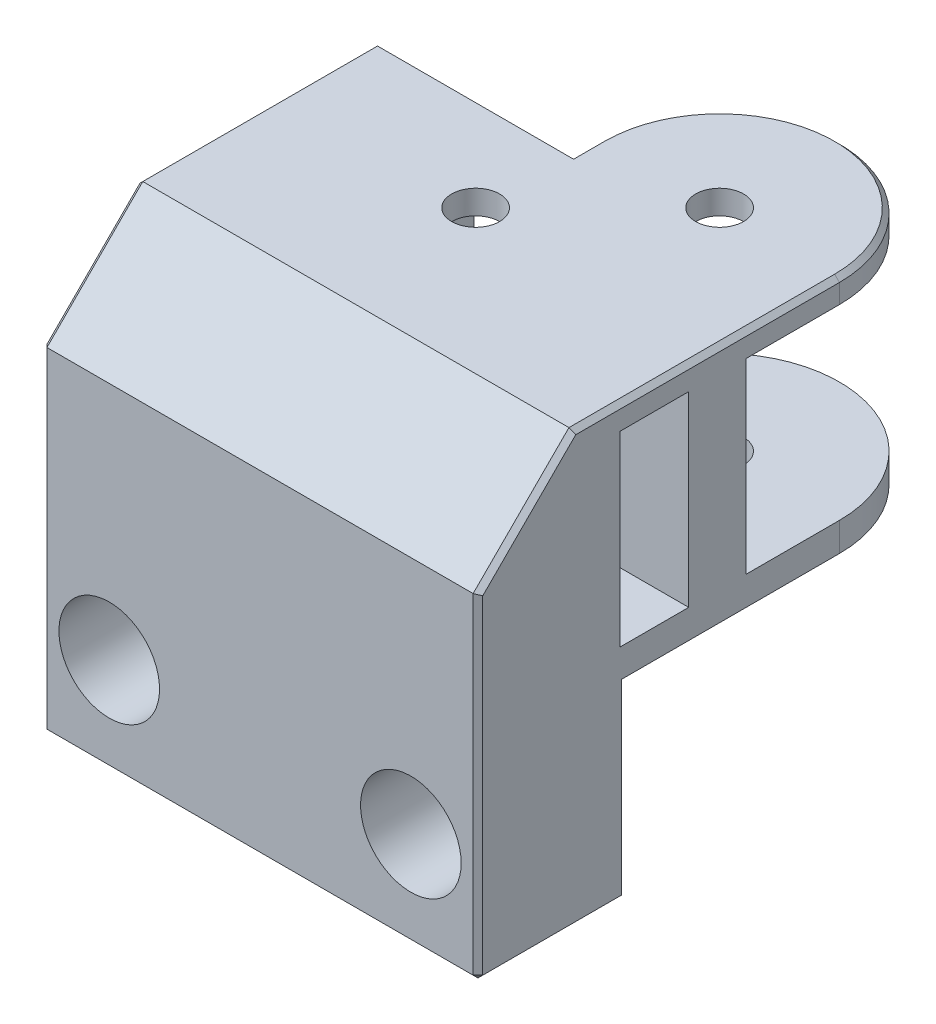
SolidWorks part; units mm, degrees
ref_plane "Front Plane" through (0, 0, 0) normal (0, 0, 1) x (1, 0, 0)
ref_plane "Top Plane" through (0, 0, 0) normal (0, 1, 0) x (1, 0, 0)
ref_plane "Right Plane" through (0, 0, 0) normal (1, 0, 0) x (0, 0, -1)
sketch "Sketch1" plane through (0, 0, 0) normal (0, 1, 0) x (1, 0, 0)
  line L0 (0, 0) -> (-20.24, 0) construction
  line L1 (20.24, -10) -> (25.24, -10)
  line L2 (-20.24, 10) -> (20.24, 10)
  line L3 (-20.24, 10) -> (-20.24, -10)
  line L4 (-20.24, -10) -> (20.24, -10)
  line L5 (20.24, 10) -> (20.24, -10) construction
  line L6 (-20.24, 10) -> (20.24, -10) construction
  line L7 (-20.24, -10) -> (20.24, 10) construction
  line L8 (25.24, -10) -> (25.24, 10)
  line L9 (25.24, 10) -> (20.24, 10)
  circle A0 centre (0, 0) radius 2.5
  point P3 (0, 0)
  dimension "D1" = 5
  dimension "D2" = 20
  dimension "D3" = 20.24
  dimension "D4" = 5
extrude "Boss-Extrude1" add sketch "Sketch1" along normal blind 25
sketch "Sketch9" plane through (0, 0, 10) normal (0, 0, 1) x (1, 0, 0)
  line L0 (25.24, 25) -> (25.24, 0) construction
  line L1 (-20.24, 25) -> (25.24, 25)
  line L2 (-20.24, 25) -> (-20.24, -20)
  line L3 (-20.24, -20) -> (25.24, -20)
  line L4 (25.24, 25) -> (25.24, -20)
  line L6 (-20.24, 0) -> (25.24, 0) construction
  dimension "D1" = 20
extrude "Boss-Extrude4" add sketch "Sketch9" along normal blind 15
sketch "Sketch10" plane through (0, 25, 0) normal (0, 1, 0) x (1, 0, 0)
  line L0 (10.16, 0) -> (10.16, 10)
  line L1 (25.24, 10) -> (-20.24, 10) construction
  line L2 (10.16, 10) -> (-10.16, 10)
  line L3 (-10.16, 10) -> (-10.16, 0)
  arc A0 (10.16, 0) -> (-10.16, 0) centre (0, 0) cw
  dimension "D1" = 10.16
extrude "Cut-Extrude2" cut sketch "Sketch10" against normal blind 19.5 from offset 2.5 offset against normal yes
sketch "Sketch14" plane through (0, 25, 0) normal (0, 1, 0) x (1, 0, 0)
  line L0 (464.5276, -6.3662) -> (392.4411, -6.3662) construction
  line L1 (55.3303, 6.3662) -> (12.7324, 6.3662) construction
  line L2 (464.5276, -6.3662) -> (392.4411, -6.3662)
  line L3 (55.3303, 6.3662) -> (12.7324, 6.3662)
  circle A0 centre (12.7324, 12.7324) radius 9.017 construction
  circle A1 centre (12.7324, 12.7324) radius 9.017
sketch "Sketch15" plane through (0, 25, 0) normal (0, 1, 0) x (1, 0, 0)
  line L0 (25.24, 10) -> (25.24, 12.7324)
  line L1 (0.2248, 12.7324) -> (0.2248, 10)
  line L2 (0.2248, 10) -> (25.24, 10)
  arc A0 (25.24, 12.7324) -> (0.2248, 12.7324) centre (12.7324, 12.7324) ccw
  circle A1 centre (12.7324, 12.7324) radius 2.5
  dimension "D1" = 5
extrude "Boss-Extrude5" add sketch "Sketch15" against normal up to surface (25 mm away) up to face at (2.5, 0, 0)
chamfer "Chamfer1" distance 10 angle 45 1 edges at (2.5, 25, 25)
ref_axis "Axis1" through (0, 3, 0) along (0, -1, 0)
ref_plane "Plane1" through (0, 0, 0) normal (-1, 0, 0) x (0, 0, 1)
sketch "Sketch16" plane through (25.24, 0, 0) normal (1, 0, 0) x (0, 0, -1)
  line L0 (-10.16, 22.5) -> (-10.16, 3) construction
  line L1 (-10.16, 3) -> (29.84, 3)
  line L2 (-10.16, 3) -> (-10.16, 22.5)
  line L3 (-10.16, 22.5) -> (29.84, 22.5)
  line L4 (29.84, 3) -> (29.84, 22.5)
  line L5 (2.5, 3) -> (-2.5, 3) construction
  line L6 (-2.5, 22.5) -> (2.5, 22.5) construction
  dimension "D1" = 40
extrude "Cut-Extrude3" cut sketch "Sketch16" against normal up to surface (25.24 mm away) up to plane "Plane1"
sketch "Sketch11" plane through (0, 0, 25) normal (0, 0, 1) x (1, 0, 0)
  line L0 (-20.24, -10) -> (25.24, -10) construction
  line L1 (25.24, -20) -> (25.24, 15) construction
  line L2 (-20.24, 15) -> (-20.24, -20) construction
  line L3 (-20.24, -20) -> (25.24, -20) construction
  circle A0 centre (-13.24, -10) radius 7
  circle A1 centre (18.24, -10) radius 7
  dimension "D2" = 14
  dimension "D1" = 10
sketch "Sketch17" plane through (0, 25, 0) normal (0, 1, 0) x (1, 0, 0)
  line L0 (0, 0) -> (10.16, 0) construction
  line L1 (10.16, 0) -> (25.24, 0) construction
  line L2 (25.24, -10.16) -> (25.24, 12.7324) construction
  line L3 (10.16, -3) -> (25.24, -3)
  line L4 (10.16, 3) -> (25.24, 3)
  line L5 (10.16, -3) -> (10.16, 3)
  line L6 (25.24, -3) -> (25.24, 3)
  dimension "D1" = 10.16
  dimension "D2" = 3
  dimension "D3" = 3
extrude "Boss-Extrude6" add sketch "Sketch17" against normal up to surface (22 mm away) up to face at (0, 3, -2.5)
hole_wizard "CBORE for M5 SBHCS1" positions "Sketch12" profile "Sketch13" counterbore size "M5" standard "ANSI Metric" end condition through all
sketch "Sketch12" plane through (0, 0, 25) normal (0, 0, 1) x (1, 0, 0)
  point P0 (-13.24, -10)
  point P3 (18.24, -10)
sketch "Sketch13" plane through (-13.24, -10, 25) normal (1, 0, 0) x (0, -1, 0)
  line L0 (0, 0) -> (0, 50.24)
  line L1 (0, 50.24) -> (2.75, 50.24)
  line L3 (2.75, 50.24) -> (2.75, 9.75)
  line L4 (2.75, 9.75) -> (5.25, 9.75)
  line L5 (5.25, 9.75) -> (5.25, 0)
  line L7 (5.25, 0) -> (0, 0)
  line L11 (0, -6.35) -> (0, 107.95) construction
  dimension "Thru Hole Dia." = 5.5
  dimension "Thru Hole Depth" = 50.24
  dimension "C'Bore Dia." = 10.5
  dimension "C'Bore Depth" = 9.75
chamfer "Chamfer2" distance 0.5 angle 45 12 edges at (25.24, -20, 17.5) (-20.24, -20, 17.5) (-10.0076, 25, -10) (-20.24, 25, 2.5) (-20.24, 20, 20) (25.24, -2.5, 25) (2.5, -20, 25) (-20.24, -2.5, 25) (25.24, 25, 1.1338) (25.24, 20, 20) (0.2248, 25, -11.3662) (12.7324, 25, -25.24)
